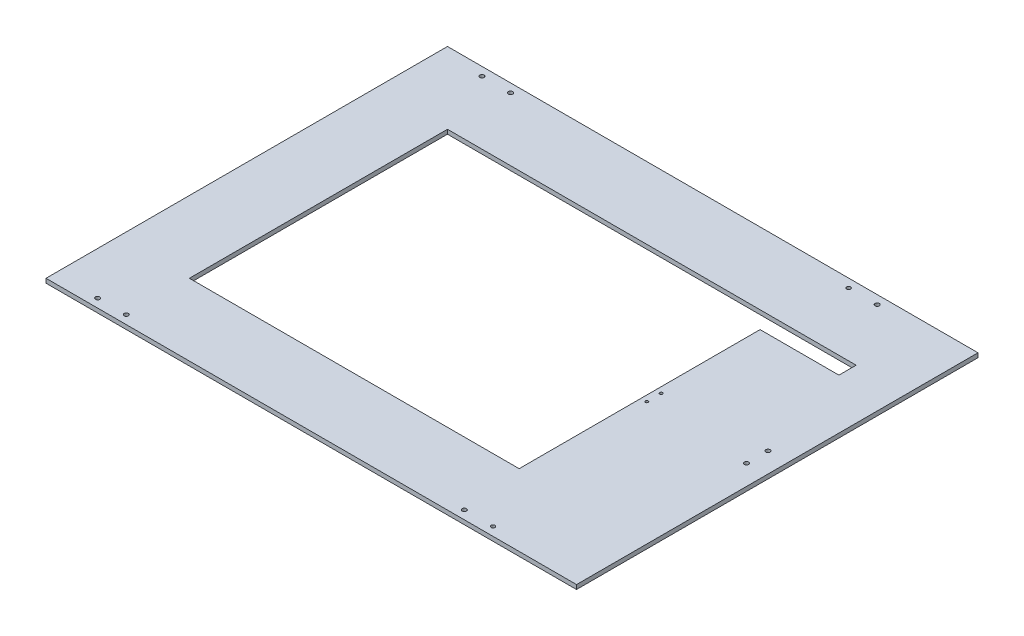
SolidWorks part; units mm, degrees
ref_plane "Front Plane" through (0, 0, 0) normal (0, 0, 1) x (1, 0, 0)
ref_plane "Top Plane" through (0, 0, 0) normal (0, 1, 0) x (1, 0, 0)
ref_plane "Right Plane" through (0, 0, 0) normal (1, 0, 0) x (0, 0, -1)
sketch "Sketch1" plane through (0, 0, 0) normal (0, 1, 0) x (1, 0, 0)
  line L1 (0, 0) -> (370, 0)
  line L2 (0, 0) -> (0, 280)
  line L3 (0, 280) -> (370, 280)
  line L4 (370, 0) -> (370, 280)
  line L5 (50, 50) -> (280, 50)
  line L6 (50, 50) -> (50, 230)
  line L7 (50, 230) -> (280, 230)
  line L8 (280, 50) -> (280, 230)
  line L9 (50, 280) -> (50, 274) construction
  line L10 (50, 274) -> (30, 274) construction
  line L12 (185, 280) -> (185, 0) construction
  line L13 (0, 140) -> (370, 140) construction
  line L14 (284, 140) -> (284, 145) construction
  line L15 (284, 140) -> (284, 135) construction
  circle A0 centre (30, 274) radius 1.5
  circle A1 centre (50, 274) radius 1.5692
  circle A2 centre (30, 6) radius 1.5
  circle A3 centre (50, 6) radius 1.5
  circle A4 centre (285.7569, 273.9854) radius 1.3573
  circle A5 centre (305.7569, 273.9346) radius 1.5
  circle A6 centre (285.7569, 6.0015) radius 1.5
  circle A7 centre (305.7569, 6.0068) radius 1.3225
  circle A8 centre (284, 145) radius 1
  circle A9 centre (284, 135) radius 1
  dimension "D11" = 3
  dimension "D12" = 2
  dimension "D1" = 370
  dimension "D2" = 280
  dimension "D3" = 230
  dimension "D4" = 50
  dimension "D5" = 50
  dimension "D6" = 50
  dimension "D8" = 6
  dimension "D10" = 20
  dimension "D13" = 4
  dimension "D14" = 10
  dimension "D15" = 20
  dimension "D16" = 20
  dimension "D17" = 20
extrude "Boss-Extrude1" add sketch "Sketch1" along normal blind 3
sketch "Sketch2" plane through (0, 3, 0) normal (0, 1, 0) x (1, 0, 0)
  line L1 (280, 230) -> (335, 230)
  line L2 (280, 230) -> (280, 218)
  line L3 (280, 218) -> (335, 218)
  line L4 (335, 230) -> (335, 218)
  dimension "D1" = 55
  dimension "D2" = 12
extrude "Cut-Extrude1" cut sketch "Sketch2" against normal blind 10
sketch "Sketch3" plane through (0, 3, 0) normal (0, 1, 0) x (1, 0, 0)
  line L0 (356, 140) -> (356, 147.5) construction
  line L1 (370, 0) -> (370, 280) construction
  line L3 (356, 147.5) -> (356, 140) construction
  line L6 (356, 140) -> (356, 132.5) construction
  circle A0 centre (356, 147.5) radius 1.5
  circle A1 centre (356, 132.5) radius 1.5
  point P5 (364.8563, 140)
  dimension "D1" = 3
  dimension "D2" = 3
  dimension "D3" = 14
  dimension "D4" = 15
extrude "Cut-Extrude2" cut sketch "Sketch3" against normal blind 10
